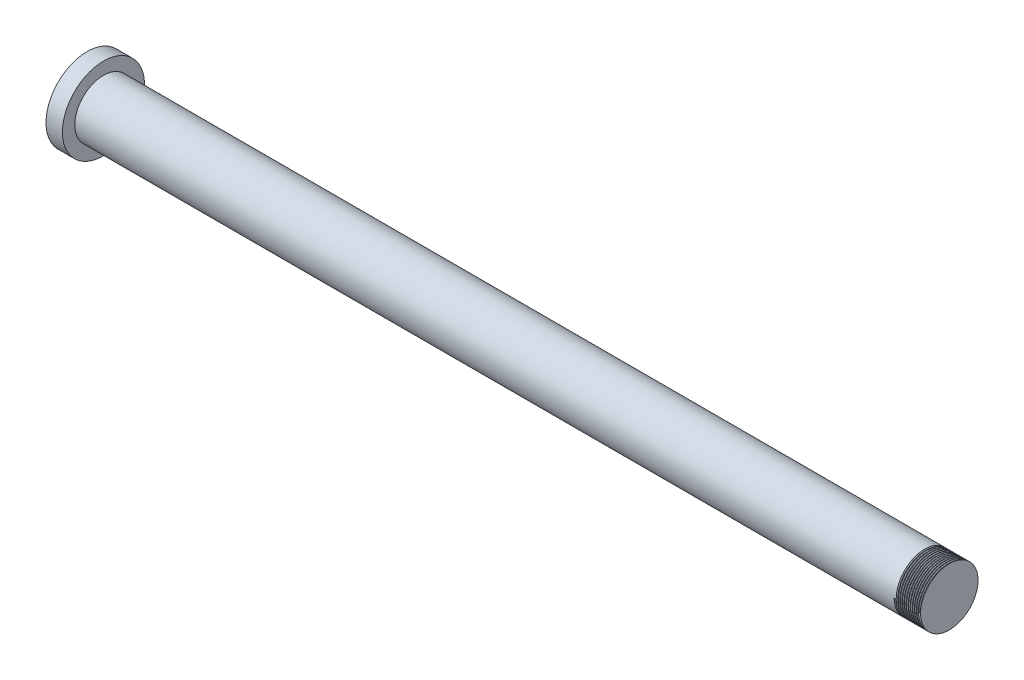
SolidWorks part; units mm, degrees
ref_plane "Front Plane" through (0, 0, 0) normal (0, 0, 1) x (1, 0, 0)
ref_plane "Top Plane" through (0, 0, 0) normal (0, 1, 0) x (1, 0, 0)
ref_plane "Right Plane" through (0, 0, 0) normal (1, 0, 0) x (0, 0, -1)
sketch "Sketch1" plane through (0, 0, 0) normal (0, 0, 1) x (1, 0, 0)
  line L0 (0, 0) -> (105, 0)
  dimension "D1" = 105
revolve "Revolve-Thin1" add sketch "Sketch1" angle 360 about L0 wall 3.5
sketch "Sketch2" plane through (0, 0, 0) normal (-1, 0, 0) x (0, 0, 1)
  circle A0 centre (0, 0) radius 5
  dimension "D1" = 10
extrude "Boss-Extrude1" add sketch "Sketch2" against normal blind 2
thread "Thread2" pitch 0.25 method cut profile "Thread Profile2" start angle 0, offset 0, length 3, pitch 0.25, diameter 7
ref_plane "Plane2" through (105, 0, 3.5) normal (0, -1, 0) x (0, 0, 1)
sketch "Thread Profile2" plane through (105, 0, 3.5) normal (0, -1, 0) x (0, 0, 1)
  line L0 (0, 0) -> (0, 0.25) construction
  line L11 (0, 0) -> (0, 0.2187)
  line L12 (0, 0.2187) -> (-0.1353, 0.1406)
  line L13 (-0.1353, 0.1406) -> (-0.1353, 0.0781)
  line L15 (-0.1353, 0.0781) -> (0, 0)
  line L17 (-0.1353, 0.1094) -> (0, 0.1094) construction
  point P2 (0, 0)
  dimension "Pitch" = 0.25
  dimension "Profile_Angle" = 60
  dimension "Profile_Land" = 0.0625
  dimension "Profile_Height" = 0.1353
equation "\"7.9.00mm\"=10"
